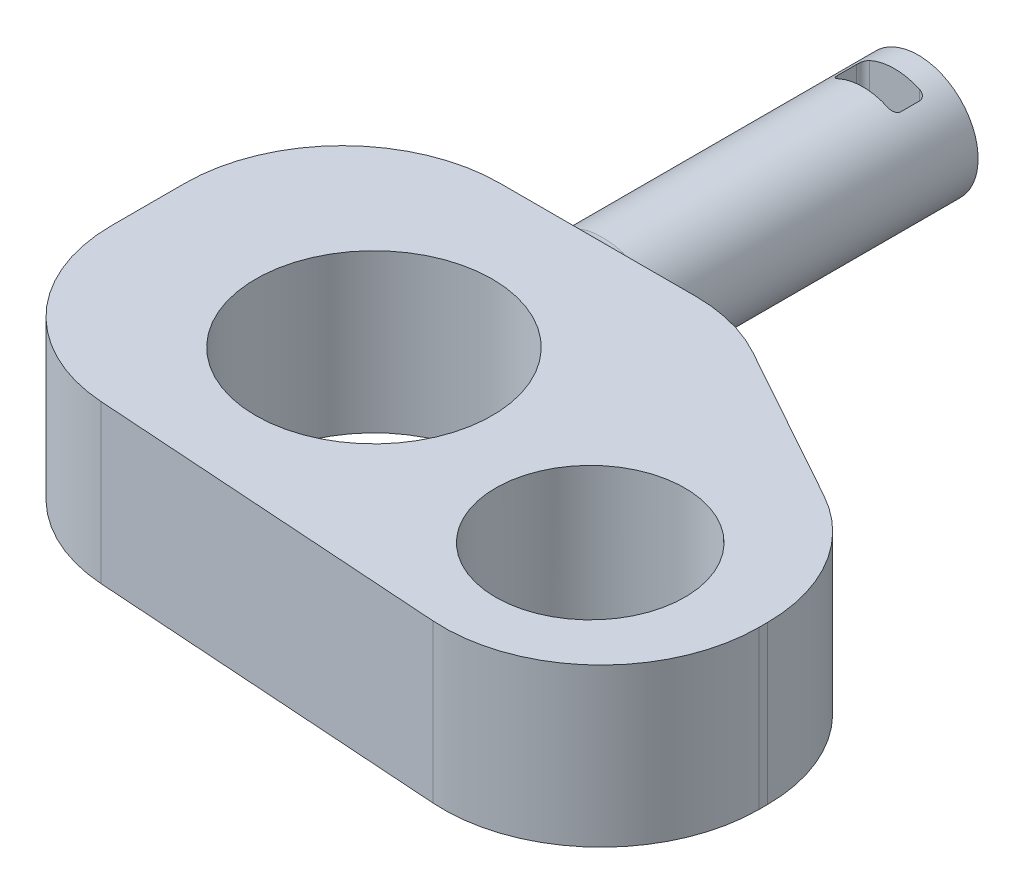
SolidWorks part; units mm, degrees
ref_plane "Front" through (0, 0, 0) normal (0, 0, 1) x (1, 0, 0)
ref_plane "Top" through (0, 0, 0) normal (0, 1, 0) x (1, 0, 0)
ref_plane "Right" through (0, 0, 0) normal (1, 0, 0) x (0, 0, -1)
sketch "Sketch1" plane through (0, 0, 0) normal (0, 0, 1) x (1, 0, 0)
  circle A0 centre (0, 0) radius 5
  dimension "D1" = 10
extrude "Boss-Extrude1" add sketch "Sketch1" along normal blind 20
sketch "Sketch2" plane through (0, 0, 0) normal (0, 0, -1) x (-1, 0, 0)
  circle A0 centre (0, 0) radius 3.98
  circle A1 centre (0, 0) radius 5 construction
  circle A2 centre (0, 0) radius 5
  dimension "D1" = 7.96
extrude "Cut-Extrude2" cut sketch "Sketch2" against normal blind 8 contours A0 | A2
sketch "Sketch8" plane through (0, 0, 20) normal (0, 0, 1) x (1, 0, 0)
  circle A0 centre (0, 0) radius 5
  dimension "D1" = 10
extrude "Boss-Extrude2" add sketch "Sketch8" along normal blind 20
sketch "Sketch9" plane through (0, 0, 40) normal (0, 0, 1) x (1, 0, 0)
  line L1 (0, 5) -> (35, 5)
  line L3 (0, -5) -> (35, -5)
  line L4 (35, 5) -> (35, -5)
  circle A1 centre (0, 0) radius 5 construction
  arc A2 (0, -5) -> (0, 5) centre (0, 0) ccw
  dimension "D1" = 35
  dimension "D2" = 5
  dimension "D3" = 10
extrude "Boss-Extrude3" add sketch "Sketch9" against normal blind 31.5
sketch "Sketch10" plane through (0, 0, 40) normal (0, 0, 1) x (1, 0, 0)
  line L5 (0, 5) -> (-15, 5)
  line L7 (0, -5) -> (-15, -5)
  line L8 (-15, 5) -> (-15, -5)
  arc A0 (0, 5) -> (0, -5) centre (0, 0) ccw construction
  arc A1 (0, 5) -> (0, -5) centre (0, 0) ccw
  dimension "D1" = 15
extrude "Boss-Extrude4" add sketch "Sketch10" against normal blind 31.5
sketch "Sketch12" plane through (0, 5, 0) normal (0, 1, 0) x (1, 0, 0)
  line L0 (0, -8.5) -> (-15, -8.5) construction
  line L3 (0, -21.5) -> (73.8631, -37.7534) construction
  line L4 (0, -21.5) -> (73.9968, -21.5) construction
  circle A0 centre (0, -21.5) radius 7.5
  circle A3 centre (17.5794, -25.3683) radius 6
  dimension "D1" = 15
  dimension "D3" = 12.41
  dimension "D4" = 12
  dimension "D2" = 13
  dimension "D5" = 18
extrude "Cut-Extrude3" cut sketch "Sketch12" against normal blind 31.5
sketch "Sketch14" plane through (0, 5, 0) normal (0, 1, 0) x (1, 0, 0)
  line L1 (35, -8.5) -> (0, -8.5) construction
  line L2 (35, -8.5) -> (35, -40) construction
  line L4 (-15, -8.5) -> (-15, -40) construction
  line L6 (-15, -40) -> (35, -40)
  line L7 (35, -40) -> (35, -37.3683)
  line L8 (27.5794, -35.3683) -> (-15, -32.5)
  line L9 (-15, -32.5) -> (-15, -40)
  line L10 (27.5794, -18.2519) -> (27.5794, -35.3683)
  line L11 (-15, -40) -> (35, -40)
  line L12 (35, -40) -> (35, -8.5)
  line L13 (35, -8.5) -> (0, -8.5)
  line L14 (0, -8.5) -> (-15, -8.5)
  line L15 (-15, -8.5) -> (-15, -40)
  line L18 (35, -8.5) -> (10, -8.5)
  line L22 (35, -37.3683) -> (35, -8.5)
  line L23 (10, -8.5) -> (27.5794, -18.2519)
  circle A0 centre (0, -21.5) radius 7.5 construction
  dimension "D2" = 10
  dimension "D3" = 11
  dimension "D4" = 7.1164
  dimension "D6" = 10
  dimension "D7" = 10
  dimension "D1" = 0
extrude "Cut-Extrude4" cut sketch "Sketch14" against normal through all
fillet "Fillet1" radius 10 5 edges at (-15, 0, 8.5) (-15, 0, 32.5) (27.5794, 0, 35.3683) (27.5794, 0, 18.2519) (10, 0, 8.5)
sketch "Sketch15" plane through (0, 5, 0) normal (0, 1, 0) x (1, 0, 0)
  line L0 (0, -21.5) -> (57.2418, -34.0932)
  line L1 (0, -21.5) -> (51.5086, -21.5)
  dimension "D1" = 12.407
sketch "Sketch17" plane through (0, 0, 0) normal (0, 0, -1) x (-1, 0, 0)
  circle A1 centre (0, 0) radius 3.98
  circle A2 centre (0, 0) radius 3.98
  dimension "D1" = 0
extrude "Boss-Extrude5" add sketch "Sketch17" along normal blind 13
sketch "Sketch18" plane through (0, 5, 0) normal (0, 1, 0) x (1, 0, 0)
  line L0 (-3.98, 8) -> (3.98, 8) construction
  line L1 (-3.98, 13) -> (-3.98, -8) construction
  line L2 (3.98, -8) -> (3.98, 13) construction
  line L3 (3.98, 13) -> (-3.98, 13) construction
  line L4 (0, 8) -> (0, 13) construction
  line L5 (-1.6, 11.5) -> (1.6, 11.5)
  line L6 (-2, 11.1) -> (-2, 9.9)
  line L7 (-1.6, 9.5) -> (1.6, 9.5)
  line L8 (2, 11.1) -> (2, 9.9)
  line L9 (-2, 10.5) -> (2, 10.5) construction
  arc A0 (1.6, 11.5) -> (2, 11.1) centre (1.6, 11.1) cw
  arc A1 (1.6, 9.5) -> (2, 9.9) centre (1.6, 9.9) ccw
  arc A2 (-2, 9.9) -> (-1.6, 9.5) centre (-1.6, 9.9) ccw
  arc A3 (-1.6, 11.5) -> (-2, 11.1) centre (-1.6, 11.1) ccw
  point P14 (0, 10.5)
  point P17 (0, 10.5)
  point P22 (2, 11.5)
  point P25 (2, 9.5)
  point P30 (-2, 11.5)
  dimension "D4" = 0.4
  dimension "D1" = 5
  dimension "D2" = 2
  dimension "D3" = 4
extrude "Cut-Extrude5" cut sketch "Sketch18" against normal through all
sketch "Sketch19" plane through (0, 0, 8) normal (0, 0, -1) x (-1, 0, 0)
  circle A0 centre (0, 0) radius 5 construction
  circle A1 centre (0, 0) radius 3.98
  circle A2 centre (0, 0) radius 3.98
  circle A3 centre (0, 0) radius 5
  dimension "D1" = 0
extrude "Cut-Extrude6" cut sketch "Sketch19" against normal up to surface (0.5 mm away) up to face at (4.956, 0, 8.5)
sketch "Sketch20" plane through (0, 0, -13) normal (0, 0, -1) x (-1, 0, 0)
  circle A0 centre (0, 0) radius 3.8
  circle A1 centre (0, 0) radius 3.98 construction
  circle A2 centre (0, 0) radius 3.98
  dimension "D1" = 7.6
extrude "Cut-Extrude7" cut sketch "Sketch20" against normal up to surface (21.5 mm away) up to face at (1.206, 0, 8.5)
fillet "Fillet2" radius 1.5 1 edges at (3.8, 0, 8.5)
